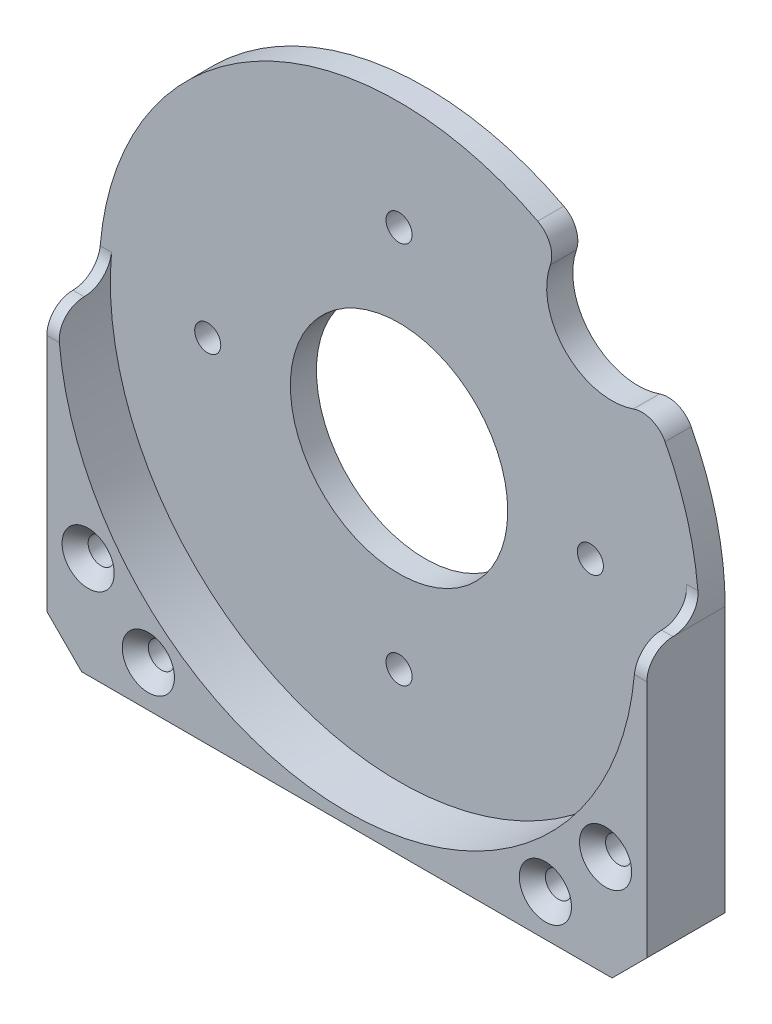
SolidWorks part; units mm, degrees
ref_plane "Спереди" through (0, 0, 0) normal (0, 0, 1) x (1, 0, 0)
ref_plane "Сверху" through (0, 0, 0) normal (0, 1, 0) x (1, 0, 0)
ref_plane "Справа" through (0, 0, 0) normal (1, 0, 0) x (0, 0, -1)
sketch "Эскиз1" plane through (0, 0, 0) normal (0, 0, 1) x (1, 0, 0)
  circle A0 centre (0, 0) radius 34.5
  dimension "D1" = 69
extrude "Бобышка-Вытянуть1" add sketch "Эскиз1" along normal blind 3
sketch "Эскиз2" plane through (0, 0, 3) normal (0, 0, 1) x (1, 0, 0)
  line L0 (-34.5, 0) -> (34.5, 0)
  circle A0 centre (0, 0) radius 33.2
  circle A1 centre (0, 0) radius 34.5
  circle A2 centre (0, 0) radius 34.5 construction
  circle M2 centre (0, 0) radius 34.5
  dimension "D1" = 66.4
extrude "Бобышка-Вытянуть2" add sketch "Эскиз2" along normal blind 6 contours A0 L0 M2
sketch "Эскиз3" plane through (0, 0, 0) normal (0, 0, -1) x (-1, 0, 0)
  line L1 (-34.5, 0) -> (34.5, 0)
  line L2 (-34.5, 0) -> (-34.5, -34.5)
  line L3 (-34.5, -34.5) -> (34.5, -34.5)
  line L4 (34.5, 0) -> (34.5, -34.5)
  circle A0 centre (0, 0) radius 34.5 construction
  circle M5 centre (0, 0) radius 34.5
  dimension "D1" = 69
extrude "Бобышка-Вытянуть3" add sketch "Эскиз3" against normal blind 9 contours L2 L3 M5 | L4 L3 M5
fillet "Скругление1" radius 3 2 edges at (-33.85, 0, 3) (33.85, 0, 3)
sketch "Эскиз4" plane through (0, 0, 3) normal (0, 0, 1) x (1, 0, 0)
  circle A0 centre (0, 0) radius 12.5
  dimension "D1" = 25
extrude "Вырез-Вытянуть1" cut sketch "Эскиз4" against normal blind 9
sketch "Эскиз5" plane through (0, 0, 3) normal (0, 0, 1) x (1, 0, 0)
  circle A0 centre (0, 0) radius 22 construction
  circle A1 centre (0, 22) radius 1.5
  circle A2 centre (22, 0) radius 1.5
  circle A3 centre (0, -22) radius 1.5
  circle A4 centre (-22, 0) radius 1.5
  point P5 (0, -22)
  point P14 (0, 0)
  dimension "D1" = 44
  dimension "D2" = 3
  dimension "D3" = 4
extrude "Вырез-Вытянуть2" cut sketch "Эскиз5" against normal blind 9
sketch "Эскиз6" plane through (0, 0, 0) normal (0, 0, -1) x (-1, 0, 0)
  line L0 (0, 0) -> (-32.8366, 32.8366) construction
  line L1 (0, 0) -> (-50.1524, 0) construction
  circle A0 centre (-24.4749, 24.4749) radius 7.5
  dimension "D2" = 15
  dimension "D1" = 45
extrude "Вырез-Вытянуть3" cut sketch "Эскиз6" against normal blind 9
fillet "Скругление2" radius 3 1 edges at (29.0835, 18.5579, 1.5)
sketch "Эскиз7" plane through (0, 0, 9) normal (0, 0, 1) x (1, 0, 0)
  line L0 (0, 0) -> (-29.8056, -38.8434) construction
  line L1 (0, 0) -> (-41.1288, -41.1288) construction
  line L2 (0, 0) -> (-51.0432, 0) construction
  line L3 (0, 0) -> (-43.0452, -33.0297) construction
  line L4 (0, 0) -> (0, -46.6338) construction
  circle A0 centre (0, 0) radius 37.5 construction
  circle A1 centre (-29.7508, -22.8286) radius 1.5
  circle A2 centre (-22.8286, -29.7508) radius 1.5
  circle A3 centre (29.7508, -22.8286) radius 1.5
  circle A4 centre (22.8286, -29.7508) radius 1.5
  dimension "D1" = 75
  dimension "D5" = 3
  dimension "D6" = 3
  dimension "D2" = 45
  dimension "D3" = 7.5
  dimension "D4" = 7.5
extrude "Вырез-Вытянуть4" cut sketch "Эскиз7" against normal blind 9
chamfer "Фаска1" distance 1.5 angle 45 4 edges at (28.2508, -22.8286, 9) (21.3286, -29.7508, 9) (-21.3286, -29.7508, 9) (-28.2508, -22.8286, 9)
chamfer "Фаска2" distance 4 angle 45 2 edges at (34.5, -34.5, 4.5) (-34.5, -34.5, 4.5)
